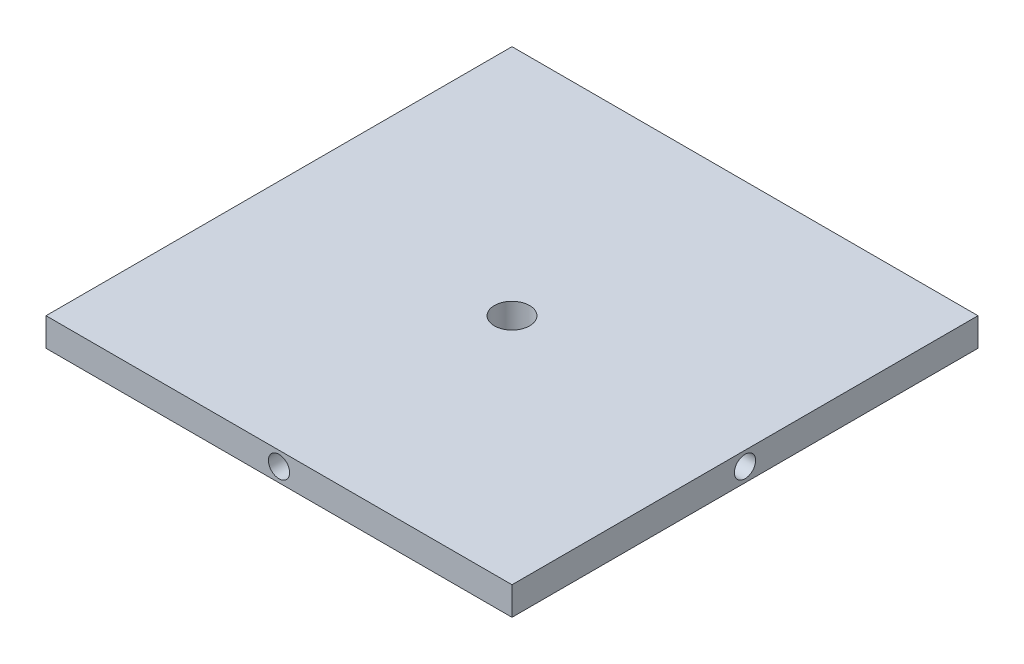
SolidWorks part; units mm, degrees
material "6061-T6 (SS)"
ref_plane "Front Plane" through (0, 0, 0) normal (0, 0, 1) x (1, 0, 0)
ref_plane "Top Plane" through (0, 0, 0) normal (0, 1, 0) x (1, 0, 0)
ref_plane "Right Plane" through (0, 0, 0) normal (1, 0, 0) x (0, 0, -1)
ref_plane "Plane1" through (0, 12.7, 0) normal (0, 1, 0) x (1, 0, 0)
sketch "Sketch1" plane through (0, 0, 0) normal (0, 1, 0) x (1, 0, 0)
  line L1 (-209.55, -209.55) -> (209.55, -209.55)
  line L2 (-209.55, -209.55) -> (-209.55, 209.55)
  line L3 (-209.55, 209.55) -> (209.55, 209.55)
  line L4 (209.55, -209.55) -> (209.55, 209.55)
  line L5 (-209.55, -209.55) -> (209.55, 209.55) construction
  line L6 (-209.55, 209.55) -> (209.55, -209.55) construction
  circle A0 centre (0, 0) radius 15.875
  point P0 (0, 0)
  dimension "D3" = 31.75
  dimension "D1" = 419.1
  dimension "D2" = 419.1
extrude "Boss-Extrude1" add sketch "Sketch1" along normal blind 25.4
ref_axis "Axis1" through (0, 12.7, -265.43) along (0, 0, 1)
ref_axis "Axis2" through (265.43, 12.7, 0) along (-1, 0, 0)
hole_wizard "3/4 (0.75) Diameter Hole2" positions "Sketch4" profile "Sketch5" hole size "3/4" standard "ANSI Inch"
sketch "Sketch4" plane through (209.55, 0, 0) normal (1, 0, 0) x (0, 0, -1)
  point P0 (0, 12.7)
sketch "Sketch5" plane through (209.55, 12.7, 0) normal (0, 1, 0) x (0, 0, -1)
  line L0 (0, 0) -> (0, 81.9232)
  line L1 (0, 81.9232) -> (9.525, 76.2)
  line L2 (9.525, 76.2) -> (9.525, 0)
  line L5 (9.525, 0) -> (0, 0)
  line L10 (0, 81.9232) -> (-9.525, 76.2) construction
  line L11 (0, -6.35) -> (0, 107.95) construction
  dimension "Hole Dia." = 19.05
  dimension "Hole Depth" = 76.2
  dimension "Drill Angle" = 118
hole_wizard "3/4 (0.75) Diameter Hole1" positions "Sketch2" profile "Sketch3" hole size "3/4" standard "ANSI Inch"
sketch "Sketch2" plane through (0, 0, 209.55) normal (0, 0, 1) x (1, 0, 0)
  point P0 (0, 12.7)
sketch "Sketch3" plane through (0, 12.7, 209.55) normal (1, 0, 0) x (0, -1, 0)
  line L0 (0, 0) -> (0, 81.9232)
  line L1 (0, 81.9232) -> (9.525, 76.2)
  line L2 (9.525, 76.2) -> (9.525, 0)
  line L5 (9.525, 0) -> (0, 0)
  line L10 (0, 81.9232) -> (-9.525, 76.2) construction
  line L11 (0, -6.35) -> (0, 107.95) construction
  dimension "Hole Dia." = 19.05
  dimension "Hole Depth" = 76.2
  dimension "Drill Angle" = 118
